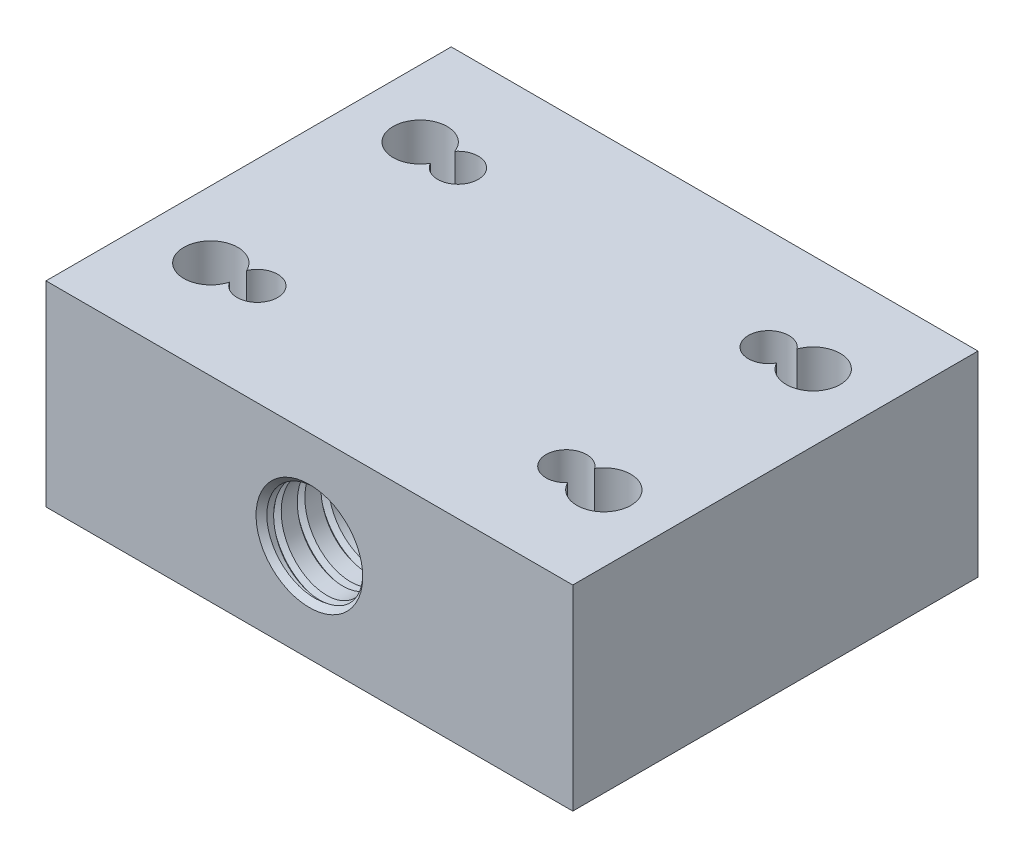
SolidWorks part; units mm, degrees
ref_plane "Front Plane" through (0, 0, 0) normal (0, 0, 1) x (1, 0, 0)
ref_plane "Top Plane" through (0, 0, 0) normal (0, 1, 0) x (1, 0, 0)
ref_plane "Right Plane" through (0, 0, 0) normal (1, 0, 0) x (0, 0, -1)
sketch "Sketch2" plane through (0, 0, 0) normal (0, 1, 0) x (1, 0, 0)
  line L1 (-39, -30) -> (39, -30)
  line L2 (-39, -30) -> (-39, 30)
  line L3 (-39, 30) -> (39, 30)
  line L4 (39, -30) -> (39, 30)
  line L5 (-39, -30) -> (39, 30) construction
  line L6 (-39, 30) -> (39, -30) construction
  point P0 (0, 0)
  dimension "D1" = 78
  dimension "D2" = 60
extrude "Boss-Extrude2" add sketch "Sketch2" along normal blind 29
sketch "Sketch3" plane through (0, 0, 0) normal (0, -1, 0) x (1, 0, 0)
  circle A0 centre (-29.1, -15.5) radius 4
  circle A1 centre (-29.1, 15.5) radius 4
  circle A2 centre (29.1, 15.5) radius 4
  circle A3 centre (29.1, -15.5) radius 4
  point P6 (-29.1, 15.5)
  point P7 (29.1, 15.5)
  point P8 (29.1, -15.5)
  point P9 (-29.1, -15.5)
  dimension "D9" = 8
  dimension "D10" = 8
  dimension "D11" = 8
  dimension "D12" = 8
  dimension "D1" = 58.2
  dimension "D2" = 58.2
  dimension "D3" = 31
  dimension "D4" = 31
sketch "Sketch4" plane through (0, 0, 30) normal (0, 0, 1) x (1, 0, 0)
  circle A0 centre (0, 14.5) radius 7.1
  point P6 (0, 14.5)
  dimension "D1" = 14.2
extrude "Cut-Extrude1" cut sketch "Sketch4" against normal through all
chamfer "Chamfer1" distance 0.8 angle 45 2 edges at (7.1, 14.5, 30) (7.1, 14.5, -30)
sketch "Sketch8" plane through (0, 29, 0) normal (0, 1, 0) x (1, 0, 0)
  line L0 (-39, 30) -> (-39, -30) construction
  line L1 (-39, -30) -> (39, -30) construction
  circle A0 centre (-23, 15) radius 3
  circle A1 centre (23, 15) radius 3
  circle A2 centre (23.2924, -15.2498) radius 3
  circle A3 centre (-22.7076, -15) radius 3
  point P0 (-23, 15)
  point P1 (23, 15)
  point P2 (23.2924, -15.2498)
  point P3 (-22.7076, -15)
  dimension "D6" = 6
  dimension "D7" = 6
  dimension "D8" = 6
  dimension "D9" = 6
  dimension "D1" = 46
  dimension "D2" = 46
  dimension "D3" = 30
  dimension "D4" = 16
  dimension "D5" = 15
extrude "Cut-Extrude2" cut sketch "Sketch8" against normal blind 20
thread "Thread1" pitch 1.5 method cut profile "Thread Profile2" start angle 0, offset 5, length 0, pitch 3.5, diameter 14.2
ref_plane "Plane2" through (7.1, 14.5, -34.2) normal (0, -1, 0) x (1, 0, 0)
sketch "Thread Profile2" plane through (7.1, 14.5, -34.2) normal (0, -1, 0) x (1, 0, 0)
  line L0 (0, 0) -> (0, 1.5) construction
  line L1 (0, 0) -> (0.8119, 0.4687)
  line L2 (0.8119, 0.4687) -> (0.8119, 0.6562)
  line L3 (0.8119, 0.6562) -> (0, 1.125)
  line L4 (0.8119, 0.5625) -> (0, 0.5625) construction
  line L11 (0, 0) -> (0, 1.125)
  point P2 (0, 0)
  dimension "Pitch" = 1.5
  dimension "Profile_Angle" = 60
  dimension "Profile_Land" = 0.1875
  dimension "Profile_Height" = 0.8119
extrude "Cut-Extrude3" cut sketch "Sketch3" against normal blind 30
